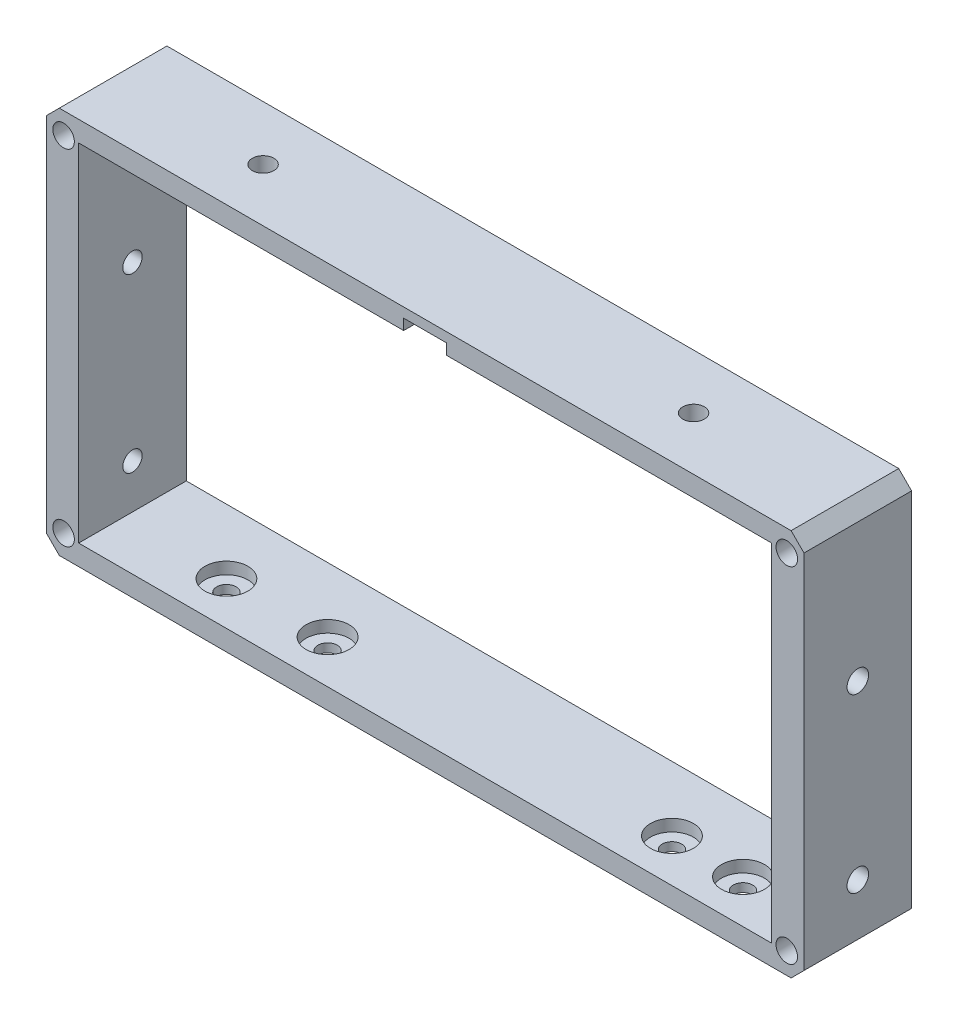
SolidWorks part; units mm, degrees
ref_plane "Front Plane" through (0, 0, 0) normal (0, 0, 1) x (1, 0, 0)
ref_plane "Top Plane" through (0, 0, 0) normal (0, 1, 0) x (1, 0, 0)
ref_plane "Right Plane" through (0, 0, 0) normal (1, 0, 0) x (0, 0, -1)
sketch "Sketch5" plane through (0, 0, 0) normal (0, 0, 1) x (1, 0, 0)
  line L1 (-80.5, -40.25) -> (80.5, -40.25)
  line L2 (-80.5, -40.25) -> (-80.5, 40.25)
  line L3 (-80.5, 40.25) -> (80.5, 40.25)
  line L4 (80.5, -40.25) -> (80.5, 40.25)
  line L5 (-80.5, -40.25) -> (80.5, 40.25) construction
  line L6 (-80.5, 40.25) -> (80.5, -40.25) construction
  line L7 (-88, -45) -> (88, -45)
  line L8 (-88, -45) -> (-88, 45)
  line L9 (-88, 45) -> (88, 45)
  line L10 (88, -45) -> (88, 45)
  line L11 (-88, -45) -> (88, 45) construction
  line L12 (-88, 45) -> (88, -45) construction
  point P0 (0, 0)
  point P6 (0, 0)
  dimension "D1" = 161
  dimension "D2" = 80.5
  dimension "D3" = 176
  dimension "D4" = 90
extrude "Boss-Extrude2" add sketch "Sketch5" along normal blind 25
hole_wizard "Ø5.0mm Dowel Hole1" positions "Sketch6" profile "Sketch7" hole size "Ø5.0" standard "ANSI Metric" end condition through all
sketch "Sketch6" plane through (0, 0, 0) normal (0, 0, -1) x (-1, 0, 0)
  line L1 (-84, -40) -> (84, -40)
  line L2 (-84, -40) -> (-84, 40)
  line L3 (-84, 40) -> (84, 40)
  line L4 (84, -40) -> (84, 40)
  line L5 (-84, -40) -> (84, 40) construction
  line L6 (-84, 40) -> (84, -40) construction
  point P1 (0, 0)
  point P2 (84, 40)
  point P115 (-84, -40)
  point P116 (-84, 40)
  point P117 (84, -40)
  dimension "D1" = 168
  dimension "D2" = 80
sketch "Sketch7" plane through (0, 0, 0) normal (1, 0, 0) x (0, 1, 0)
  line L0 (0, 0) -> (0, 25)
  line L1 (0, 25) -> (2.5, 25)
  line L2 (2.5, 25) -> (2.5, 0)
  line L5 (2.5, 0) -> (0, 0)
  line L11 (0, -6.35) -> (0, 107.95) construction
  dimension "Thru Hole Dia." = 5
  dimension "Thru Hole Depth" = 25
hole_wizard "CBORE for M4 SBHCS1" positions "Sketch8" profile "Sketch10" counterbore size "M4" standard "ANSI Metric" end condition through all
sketch "Sketch8" plane through (0, -40.25, 0) normal (0, 1, 0) x (1, 0, 0)
  line L0 (-56.175, -15) -> (63.825, -15)
  line L2 (-88, -25) -> (88, -25) construction
  line L3 (-80.5, -25) -> (80.5, -25) construction
  line L4 (-32.675, -15) -> (47.325, -15)
  point P1 (-56.175, -15)
  point P2 (63.825, -15)
  point P11 (-32.675, -15)
  point P12 (47.325, -15)
  dimension "D1" = 120
  dimension "D2" = 10
  dimension "D3" = 10
  dimension "D4" = 31.825
  dimension "D5" = 80
  dimension "D6" = 23.5
sketch "Sketch10" plane through (-56.175, -40.25, 15) normal (1, 0, 0) x (0, 0, 1)
  line L0 (0, 0) -> (0, 4.75)
  line L1 (0, 4.75) -> (2.25, 4.75)
  line L3 (2.25, 4.75) -> (2.25, 2.75)
  line L4 (2.25, 2.75) -> (5, 2.75)
  line L5 (5, 2.75) -> (5, 0)
  line L7 (5, 0) -> (0, 0)
  line L11 (0, -6.35) -> (0, 107.95) construction
  dimension "Thru Hole Dia." = 4.5
  dimension "Thru Hole Depth" = 4.75
  dimension "C'Bore Dia." = 10
  dimension "C'Bore Depth" = 2.75
hole_wizard "CBORE for M5 Hex Head Bolt3" positions "Sketch11" profile "Sketch12" tap size "M4x0.7" standard "ANSI Metric"
sketch "Sketch11" plane through (0, 0, 0) normal (0, 0, -1) x (-1, 0, 0)
  line L1 (-10, -42.5) -> (10, -42.5)
  line L2 (-10, -42.5) -> (-10, 42.5)
  line L3 (-10, 42.5) -> (10, 42.5)
  line L4 (10, -42.5) -> (10, 42.5)
  line L5 (-10, -42.5) -> (10, 42.5) construction
  line L6 (-10, 42.5) -> (10, -42.5) construction
  line L7 (-88, 45) -> (88, 45) construction
  point P0 (0, 0)
  point P1 (10, 42.5)
  point P48 (-10, -42.5)
  point P49 (-10, 42.5)
  point P50 (10, -42.5)
  dimension "D1" = 20
  dimension "D2" = 2.5
cosmetic thread "Hole Thread5" parameters "D1"=25, "D2"=4
cosmetic thread "Hole Thread6" parameters "D1"=25, "D2"=4
cosmetic thread "Hole Thread7" parameters "D1"=25, "D2"=4
cosmetic thread "Hole Thread8" parameters "D1"=25, "D2"=4
sketch "Sketch12" plane through (0, 0, 0) normal (1, 0, 0) x (0, 1, 0)
  line L0 (0, 0) -> (0, 5.9914)
  line L1 (0, 5.9914) -> (1.65, 5)
  line L2 (1.65, 5) -> (1.65, 0)
  line L5 (1.65, 0) -> (0, 0)
  line L10 (0, 5.9914) -> (-1.65, 5) construction
  line L11 (0, -6.35) -> (0, 107.95) construction
  dimension "Tap Drill Dia." = 3.3
  dimension "Tap Drill Depth" = 5
  dimension "Drill Angle" = 118
hole_wizard "CBORE for M5 Hex Head Bolt4" positions "Sketch13" profile "Sketch14" counterbore size "M5" standard "ANSI Metric" end condition up to next
sketch "Sketch13" plane through (0, 45, 0) normal (0, 1, 0) x (1, 0, 0)
  line L0 (-50, -12.6553) -> (50, -12.6553)
  point P1 (-50, -12.6553)
  point P2 (50, -12.6553)
  point P5 (0, -12.6553)
  dimension "D1" = 100
sketch "Sketch14" plane through (-50, 45, 12.6553) normal (1, 0, 0) x (0, 0, 1)
  line L0 (0, 0) -> (0, 4.75)
  line L1 (0, 4.75) -> (2.25, 4.75)
  line L3 (2.25, 4.75) -> (2.25, 4.2)
  line L4 (2.25, 4.2) -> (2.5, 4.2)
  line L5 (2.5, 4.2) -> (2.5, 0)
  line L7 (2.5, 0) -> (0, 0)
  line L11 (0, -6.35) -> (0, 107.95) construction
  dimension "Thru Hole Dia." = 4.5
  dimension "Thru Hole Depth" = 4.75
  dimension "C'Bore Dia." = 5
  dimension "C'Bore Depth" = 4.2
sketch "Sketch15" plane through (0, 0, 0) normal (0, 0, -1) x (-1, 0, 0)
  line L0 (-80.5, 40.25) -> (80.5, 40.25) construction
  line L1 (-5, 42.75) -> (5, 42.75)
  line L2 (-5, 42.75) -> (-5, 40.25)
  line L3 (-5, 40.25) -> (5, 40.25)
  line L4 (5, 42.75) -> (5, 40.25)
  line L5 (-5, 42.75) -> (5, 40.25) construction
  line L6 (-5, 40.25) -> (5, 42.75) construction
  point P0 (0, 41.5)
  dimension "D1" = 2.5
  dimension "D2" = 10
extrude "Cut-Extrude1" cut sketch "Sketch15" against normal through all
chamfer "Chamfer1" distance 3 angle 45 4 edges at (-88, 45, 12.5) (-88, -45, 12.5) (88, -45, 12.5) (88, 45, 12.5)
hole_wizard "CBORE for M5 Hex Head Bolt5" positions "Sketch16" profile "Sketch18" counterbore size "M5" standard "ANSI Metric"
sketch "Sketch16" plane through (88, 0, 0) normal (1, 0, 0) x (0, 0, -1)
  line L0 (-12.5, 10) -> (-12.5, -30)
  line L1 (0, -42) -> (0, 42) construction
  point P1 (-12.5, 10)
  point P2 (-12.5, -30)
  point P9 (-12.5, -10)
  dimension "D1" = 40
  dimension "D2" = 35
  dimension "D3" = 12.5
sketch "Sketch18" plane through (88, 10, 12.5) normal (0, 1, 0) x (0, 0, -1)
  line L0 (0, 0) -> (0, 11.3519)
  line L1 (0, 11.3519) -> (2.25, 10)
  line L2 (2.25, 10) -> (2.25, 4.2)
  line L3 (2.25, 4.2) -> (2.5, 4.2)
  line L4 (2.5, 4.2) -> (2.5, 0)
  line L5 (2.5, 0) -> (0, 0)
  line L10 (0, 11.3519) -> (-2.25, 10) construction
  line L11 (0, -6.35) -> (0, 107.95) construction
  dimension "Hole Dia." = 4.5
  dimension "Hole Depth" = 10
  dimension "C'Bore Dia." = 5
  dimension "C'Bore Depth" = 4.2
  dimension "Drill Angle" = 118
mirror "Mirror1" about plane through (0, 0, 0) normal (1, 0, 0) of "CBORE for M5 Hex Head Bolt5"
